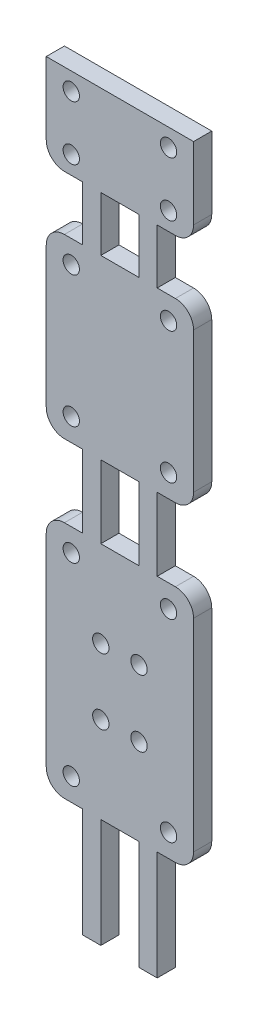
SolidWorks part; units mm, degrees
ref_plane "Front Plane" through (0, 0, 0) normal (0, 0, 1) x (1, 0, 0)
ref_plane "Top Plane" through (0, 0, 0) normal (0, 1, 0) x (1, 0, 0)
ref_plane "Right Plane" through (0, 0, 0) normal (1, 0, 0) x (0, 0, -1)
sketch "Sketch3" plane through (0, 0, 0) normal (0, 0, 1) x (1, 0, 0)
  line L0 (0, 94.0064) -> (0, 86.0614)
  line L1 (16.2, 94.0064) -> (16.2, 86.0614)
  line L2 (0, -0.1536) -> (16.2, -0.1536) construction
  line L3 (0, 76.0614) -> (0, 60.6064)
  line L4 (0, 94.0064) -> (16.2, 94.0064)
  line L5 (0, 12.3464) -> (4, 12.3464) construction
  line L6 (2, 58.6064) -> (4, 58.6064)
  line L7 (16.2, 76.0614) -> (16.2, 60.6064)
  line L8 (0, 48.6064) -> (0, 26.3464)
  line L9 (16.2, 48.6064) -> (16.2, 26.3464)
  line L10 (16.2, 12.3464) -> (16.2, -0.1536) construction
  line L11 (0, 12.3464) -> (0, -0.1536) construction
  line L12 (6, 12.3464) -> (6, 24.3464)
  line L13 (6, 24.3464) -> (10.2, 24.3464)
  line L14 (4, 12.3464) -> (4, 24.3464)
  line L15 (6, 12.3464) -> (10.2, 12.3464) construction
  line L16 (4, 50.6064) -> (4, 58.6064)
  line L17 (4, 78.0614) -> (4, 84.0614)
  line L18 (6, 50.6064) -> (6, 58.6064)
  line L19 (6, 78.0614) -> (6, 84.0614)
  line L20 (6, 84.0614) -> (10.2, 84.0614)
  line L21 (6, 78.0614) -> (10.2, 78.0614)
  line L22 (6, 58.6064) -> (10.2, 58.6064)
  line L23 (6, 50.6064) -> (10.2, 50.6064)
  line L24 (8.1, 94.0064) -> (8.1, -0.1536) construction
  line L25 (12.2, 50.6064) -> (12.2, 58.6064)
  line L26 (2, 50.6064) -> (4, 50.6064)
  line L27 (2, 24.3464) -> (4, 24.3464)
  line L28 (10.2, 12.3464) -> (10.2, 24.3464)
  line L29 (12.2, 12.3464) -> (12.2, 24.3464)
  line L30 (2, 78.0614) -> (4, 78.0614)
  line L31 (10.2, 50.6064) -> (10.2, 58.6064)
  line L32 (2, 84.0614) -> (4, 84.0614)
  line L33 (12.2, 78.0614) -> (12.2, 84.0614)
  line L34 (10.2, 78.0614) -> (10.2, 84.0614)
  line L35 (12.2, 84.0614) -> (14.2, 84.0614)
  line L36 (12.2, 78.0614) -> (14.2, 78.0614)
  line L37 (12.2, 58.6064) -> (14.2, 58.6064)
  line L38 (12.2, 50.6064) -> (14.2, 50.6064)
  line L39 (12.2, 12.3464) -> (16.2, 12.3464) construction
  line L40 (12.2, 24.3464) -> (14.2, 24.3464)
  line L41 (4, 12.3464) -> (6, 12.3464)
  line L42 (10.2, 12.3464) -> (12.2, 12.3464)
  circle A0 centre (6, 33.8464) radius 0.9
  circle A1 centre (10.2, 33.8464) radius 0.9
  circle A2 centre (2.75, 86.0614) radius 0.9
  circle A3 centre (10.2, 41.1664) radius 0.9
  circle A4 centre (13.45, 48.1064) radius 0.9
  circle A5 centre (2.75, 92.0614) radius 0.9
  circle A6 centre (13.45, 86.0614) radius 0.9
  circle A7 centre (2.75, 61.1064) radius 0.9
  arc A8 (14.2, 24.3464) -> (16.2, 26.3464) centre (14.2, 26.3464) ccw
  arc A9 (16.2, 48.6064) -> (14.2, 50.6064) centre (14.2, 48.6064) ccw
  arc A10 (2, 50.6064) -> (0, 48.6064) centre (2, 48.6064) ccw
  arc A11 (0, 26.3464) -> (2, 24.3464) centre (2, 26.3464) ccw
  arc A12 (0, 60.6064) -> (2, 58.6064) centre (2, 60.6064) ccw
  arc A13 (14.2, 58.6064) -> (16.2, 60.6064) centre (14.2, 60.6064) ccw
  arc A14 (16.2, 76.0614) -> (14.2, 78.0614) centre (14.2, 76.0614) ccw
  arc A15 (0, 76.0614) -> (2, 78.0614) centre (2, 76.0614) cw
  circle A16 centre (2.85, 9.8464) radius 0.9 construction
  circle A17 centre (13.35, 9.8464) radius 0.9 construction
  circle A18 centre (13.35, 3.8464) radius 0.9 construction
  circle A19 centre (2.85, 3.8464) radius 0.9 construction
  circle A20 centre (13.45, 61.1064) radius 0.9
  circle A21 centre (2.75, 75.5614) radius 0.9
  circle A22 centre (13.45, 26.8464) radius 0.9
  circle A23 centre (13.45, 75.5614) radius 0.9
  circle A24 centre (13.45, 92.0614) radius 0.9
  circle A25 centre (2.75, 26.8464) radius 0.9
  circle A26 centre (6, 41.1064) radius 0.9
  circle A27 centre (2.75, 48.1064) radius 0.9
  arc A28 (16.2, 86.0614) -> (14.2, 84.0614) centre (14.2, 86.0614) cw
  arc A29 (2, 84.0614) -> (0, 86.0614) centre (2, 86.0614) cw
  point P76 (16.2, 24.3464)
  point P80 (16.2, 50.6064)
  point P84 (0, 50.6064)
  point P88 (0, 24.3464)
  point P95 (0, 58.6064)
  point P99 (16.2, 58.6064)
  point P102 (16.2, 78.0614)
  point P105 (0, 78.0614)
  point P108 (16.2, 84.0614)
  point P111 (0, 84.0614)
  dimension "D49" = 1.8
  dimension "D50" = 2
  dimension "D1" = 2.5
  dimension "D2" = 9.5
  dimension "D3" = 2.5
  dimension "D4" = 9.5
  dimension "D5" = 6
  dimension "D6" = 2.75
  dimension "D7" = 2.75
  dimension "D8" = 6
  dimension "D9" = 2.5
  dimension "D10" = 2.5
  dimension "D11" = 9.5
  dimension "D12" = 9.44
  dimension "D13" = 2.75
  dimension "D14" = 6
  dimension "D15" = 2.75
  dimension "D16" = 6
  dimension "D17" = 12
  dimension "D19" = 4
  dimension "D21" = 6
  dimension "D22" = 4
  dimension "D23" = 2.85
  dimension "D24" = 2.85
  dimension "D25" = 26.26
  dimension "D26" = 16.2
  dimension "D27" = 8
  dimension "D28" = 2.5
  dimension "D29" = 2.5
  dimension "D30" = 2.75
  dimension "D31" = 2.75
  dimension "D34" = 2.5
  dimension "D35" = 2.5
  dimension "D36" = 2.75
  dimension "D37" = 2.75
  dimension "D38" = 19.455
  dimension "D39" = 6
  dimension "D40" = 2
  dimension "D41" = 2
  dimension "D42" = 2.75
  dimension "D43" = 2.75
  dimension "D46" = 2.75
  dimension "D47" = 2.75
  dimension "D48" = 9.945
  dimension "D32" = 6
  dimension "D33" = 6
  dimension "D18" = 2.5
  dimension "D44" = 2.5
  dimension "D20" = 6
  dimension "D45" = 4
extrude "Boss-Extrude3" add sketch "Sketch3" along normal blind 2
sketch "Sketch4" plane through (0, 0, 2) normal (0, 0, 1) x (1, 0, 0)
  line L0 (4, 84.0614) -> (12.2, 84.0614)
  line L1 (12.2, 84.0614) -> (12.2, 78.0614)
  line L2 (12.2, 78.0614) -> (4, 78.0614)
  line L3 (4, 78.0614) -> (4, 84.0614)
  line L4 (4, 58.6064) -> (12.2, 58.6064)
  line L5 (12.2, 58.6064) -> (12.2, 50.6064)
  line L6 (12.2, 50.6064) -> (4, 50.6064)
  line L7 (4, 50.6064) -> (4, 58.6064)
  line L8 (4, 24.3464) -> (12.2, 24.3464)
  line L9 (12.2, 24.3464) -> (12.2, 12.3464)
  line L10 (12.2, 12.3464) -> (4, 12.3464)
  line L11 (4, 12.3464) -> (4, 24.3464)
extrude "Cut-Extrude1" [suppressed] cut sketch "Sketch4" against normal up to surface (2 mm away) up to face at (1.85, 92.0614, 0)
equation "\"D25@Sketch3\"= \"HL@parametersSketch@prostheticParameters.SLDPRT\" * 0.196 - 4 - 6'Index PIP length"
equation "\"D26@Sketch3\"= \"fingerWidth@parametersSketch@prostheticParameters.SLDPRT\"'Index Width"
equation "\"D38@Sketch3\"= \"HL@parametersSketch@prostheticParameters.SLDPRT\" * 0.143 - 3 - 4 'Index MIP Length"
equation "\"D48@Sketch3\"= \"HL@parametersSketch@prostheticParameters.SLDPRT\" * 0.097 - 3 - 5'Index DIP Length - Gap Fingertip"
equation "\"D49@Sketch3\"= 1.5 + \"tol1@parametersSketch@prostheticParameters.SLDPRT\""
